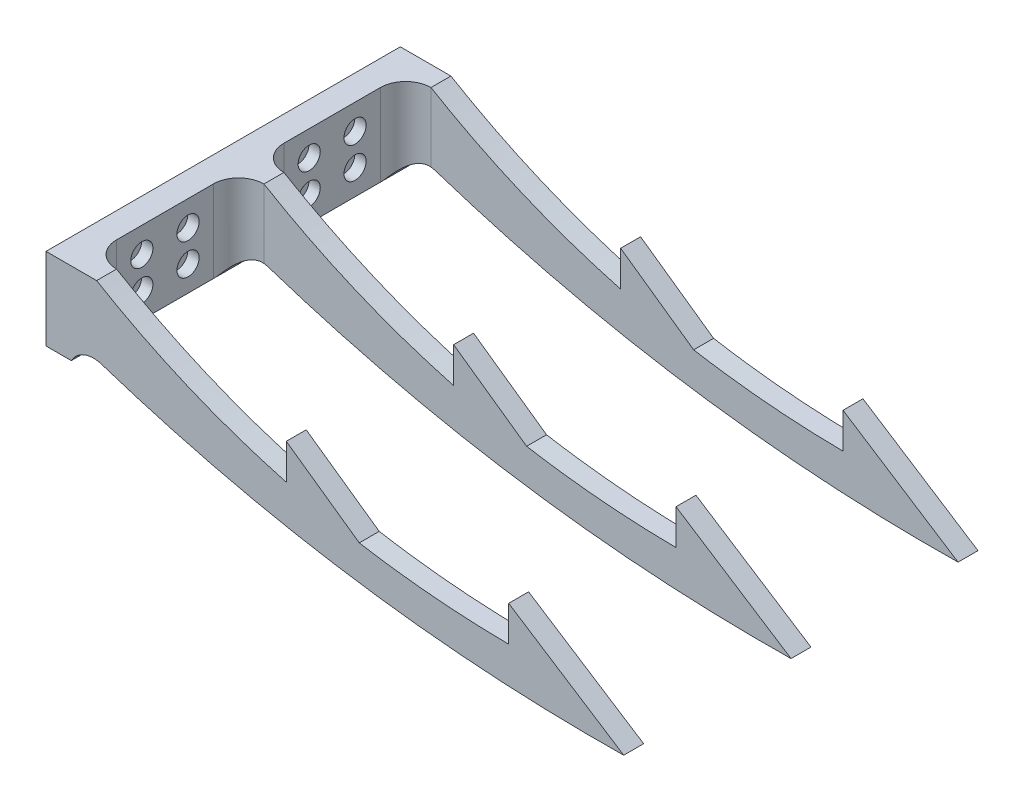
SolidWorks part; units mm, degrees
ref_plane "Front Plane" through (0, 0, 0) normal (0, 0, 1) x (1, 0, 0)
ref_plane "Top Plane" through (0, 0, 0) normal (0, 1, 0) x (1, 0, 0)
ref_plane "Right Plane" through (0, 0, 0) normal (1, 0, 0) x (0, 0, -1)
sketch "Sketch1" plane through (0, 0, 0) normal (0, 0, 1) x (1, 0, 0)
  line L0 (0, -6.35) -> (0, 6.35)
  line L1 (0, 6.35) -> (12.7, 6.35)
  line L2 (116.0939, -20.9749) -> (116.0939, -12.0849)
  line L3 (116.0939, -12.0849) -> (144.9605, -30.6605)
  line L4 (78.6103, -17.6935) -> (60.2919, -4.7804)
  line L5 (0, 12.7) -> (0, -12.7) construction
  line L6 (0, -12.7) -> (17.9605, -30.6605) construction
  line L7 (17.9605, -30.6605) -> (144.9605, -30.6605) construction
  line L8 (60.2919, -4.7804) -> (60.2919, -13.6704)
  spline S0 degree 2 poles (144.9605, -30.6605) (68.4115, -31.7178) (0, -6.35) knots 0 0 0 0.711551 0.711551 0.711551
  spline S1 degree 2 poles (116.0939, -20.9749) (96.6139, -20.8008) (78.6103, -17.6935) knots 0 0 0 0.222604 0.222604 0.222604
  spline S2 degree 3 poles (60.2919, -13.6704) (43.3593, -9.12) (27.4954, -2.4465) (12.7, 6.35) knots 0.338319 0.338319 0.338319 0.338319 0.666344 0.666344 0.666344 0.666344
  dimension "D1" = 12.7
  dimension "D2" = 12.7
  dimension "D3" = 8.89
  dimension "D4" = 8.89
  dimension "D6" = 25.4
  dimension "D8" = 25.4
  dimension "D9" = 127
extrude "Boss-Extrude1" add sketch "Sketch1" along normal blind 5
sketch "Sketch2" plane through (0, 0, 5) normal (0, 0, 1) x (1, 0, 0)
  line L1 (0, 6.35) -> (6.35, 6.35)
  line L2 (0, 6.35) -> (0, -14.224)
  line L3 (0, -14.224) -> (6.35, -14.224)
  line L4 (6.35, 6.35) -> (6.35, -14.224)
  dimension "D1" = 20.574
  dimension "D2" = 6.35
extrude "Boss-Extrude2" add sketch "Sketch2" against normal blind 88.9
ref_plane "Plane1" through (0, 0, -39.45) normal (0, 0, 1) x (1, 0, 0)
mirror "Mirror1" about plane through (0, 0, -39.45) normal (0, 0, 1) of "Boss-Extrude1"
ref_plane "Plane2" through (0, 0, -18.495) normal (0, 0, 1) x (1, 0, 0)
mirror "Mirror3" about plane through (0, 0, -18.495) normal (0, 0, 1) of "Boss-Extrude1"
fillet "Fillet1" radius 6.35 7 edges at (6.35, -8.6416, -81.4) (6.35, -8.6416, -39.49) (6.35, -8.6416, 2.5) (6.35, -1.1458, -78.9) (6.35, -1.1458, -41.99) (6.35, -1.1458, -36.99) (6.35, -1.1458, 0)
hole_wizard "CBORE for #4 Socket Head Cap Screw1" positions "Sketch3" profile "Sketch4" counterbore size "#4" standard "ANSI Inch" end condition through all
sketch "Sketch3" plane through (6.35, 15.3303, -39.45) normal (1, 0, 0) x (0, 0, -1)
  point P0 (-26.75, -23.2043)
  point P2 (-15.16, -15.3303)
  point P13 (15.24, -23.2043)
  point P15 (26.75, -15.3303)
  point P26 (-26.75, -15.3303)
  point P28 (-15.16, -23.2043)
  point P30 (15.24, -15.3303)
  point P32 (26.75, -23.2043)
sketch "Sketch4" plane through (6.35, -7.874, -12.7) normal (0, 1, 0) x (0, 0, -1)
  line L0 (0, 0) -> (0, 6.35)
  line L1 (0, 6.35) -> (1.1303, 6.35)
  line L2 (1.1303, 6.35) -> (1.1303, 2.8448)
  line L3 (1.1303, 2.8448) -> (2.7788, 2.8448)
  line L4 (2.7788, 2.8448) -> (2.7788, 0)
  line L5 (2.7788, 0) -> (0, 0)
  line L6 (0, -6.35) -> (0, 107.95) construction
  dimension "Thru Hole Dia." = 2.2606
  dimension "Thru Hole Depth" = 6.35
  dimension "C'Bore Dia." = 5.5575
  dimension "C'Bore Depth" = 2.8448
